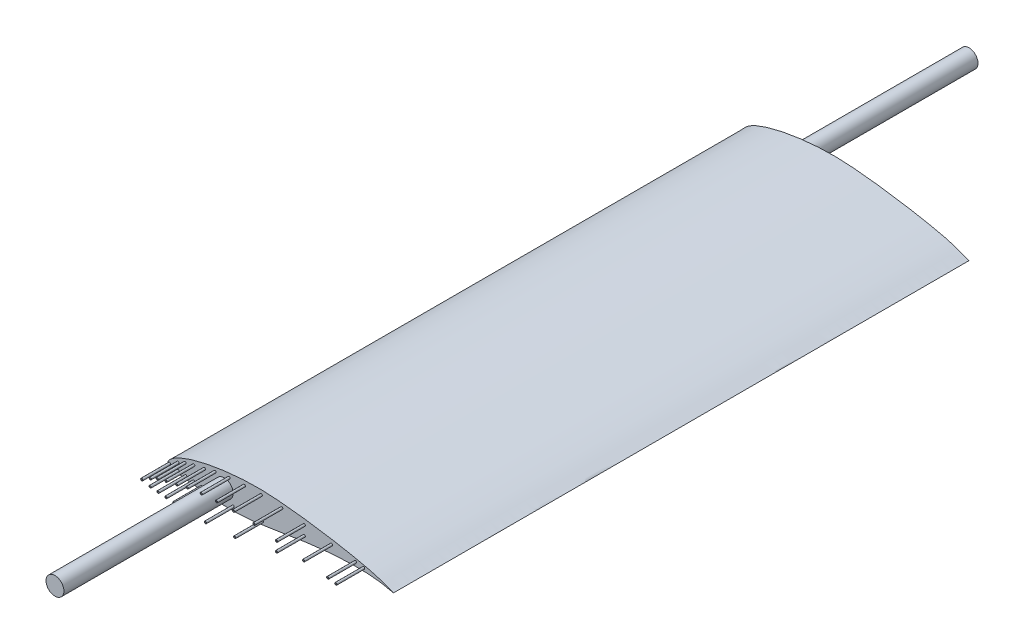
SolidWorks part; units mm, degrees
ref_plane "Front Plane" through (0, 0, 0) normal (0, 0, 1) x (1, 0, 0)
ref_plane "Top Plane" through (0, 0, 0) normal (0, 1, 0) x (1, 0, 0)
ref_plane "Right Plane" through (0, 0, 0) normal (1, 0, 0) x (0, 0, -1)
curve "Curve3"
  spline degree 3 poles (99.2573, 0.1883, 0) (100.1824, -0.0489, 0) (99.2961, 0.1993, 0) (98.6191, 0.462, 0) (97.0519, 1.0473, 0) (95.2309, 1.7549, 0) (92.9378, 2.5568, 0) (90.2536, 3.3336, 0) (87.1477, 4.0816, 0) (83.6535, 4.8449, 0) (79.8051, 5.6126, 0) (75.6551, 6.3782, 0) (71.2568, 7.1284, 0) (66.6666, 7.8484, 0) (61.9423, 8.5212, 0) (57.142, 9.1269, 0) (52.3233, 9.6447, 0) (47.5422, 10.0467, 0) (42.8474, 10.3157, 0) (38.2509, 10.3642, 0) (33.7665, 10.1859, 0) (29.4045, 9.86, 0) (25.2057, 9.3963, 0) (21.2146, 8.8145, 0) (17.4732, 8.1296, 0) (14.0211, 7.3557, 0) (10.8932, 6.51, 0) (8.1211, 5.6039, 0) (5.7296, 4.6586, 0) (3.7392, 3.6865, 0) (2.1629, 2.7162, 0) (1.0057, 1.7671, 0) (0.3099, 0.9241, 0) (0.0336, 0.3269, 0) (0.0006, 0.059, 0) (-0.0005, -0.0441, 0) (0.0087, -0.1472, 0) (0.0976, -0.2807, 0) (0.2176, -0.4056, 0) (0.6069, -0.7185, 0) (1.5156, -1.1239, 0) (3.0705, -1.583, 0) (5.1523, -2.0072, 0) (7.7279, -2.3917, 0) (10.7759, -2.7499, 0) (14.2511, -3.0772, 0) (18.0407, -3.4773, 0) (22.0414, -3.9067, 0) (26.2166, -4.1171, 0) (30.5565, -4.0983, 0) (35.1014, -3.8476, 0) (39.8555, -3.2929, 0) (44.8531, -2.5697, 0) (50.0777, -1.6972, 0) (55.4969, -0.8089, 0) (61.0345, 0.0244, 0) (66.5901, 0.7423, 0) (72.0549, 1.3013, 0) (77.3167, 1.6728, 0) (82.2608, 1.8417, 0) (86.7784, 1.812, 0) (90.7289, 1.5797, 0) (94.0476, 1.182, 0) (96.5243, 0.7715, 0) (98.476, 0.3569, 0) (99.2573, 0.1883, 0) (100.1824, -0.0489, 0) (99.2961, 0.1993, 0) knots -0.015875 -0.006971 -0.001726 0 0.001709 0.006655 0.014348 0.024259 0.036042 0.049641 0.065255 0.082793 0.102031 0.122721 0.144597 0.167375 0.190768 0.214483 0.238233 0.261741 0.284747 0.307088 0.329034 0.350455 0.371139 0.39089 0.409512 0.426831 0.442689 0.45695 0.469523 0.480322 0.48935 0.49658 0.502135 0.505254 0.506016 0.506063 0.506764 0.507486 0.508356 0.509304 0.514776 0.522722 0.53308 0.54584 0.560863 0.578018 0.596961 0.616675 0.636937 0.658148 0.680211 0.703561 0.728221 0.754164 0.781136 0.808649 0.836174 0.86317 0.889092 0.913409 0.935618 0.955187 0.97148 0.984125 0.993029 0.998274 1 1.001709 1.006655 1.014348 periodic
sketch "Sketch4" plane through (0, 0, 0) normal (0, 0, 1) x (1, 0, 0)
  spline S0 degree 3 poles (99.2573, 0.1883) (100.1824, -0.0489) (99.2961, 0.1993) (98.6191, 0.462) (97.0519, 1.0473) (95.2309, 1.7549) (92.9378, 2.5568) (90.2536, 3.3336) (87.1477, 4.0816) (83.6535, 4.8449) (79.8051, 5.6126) (75.6551, 6.3782) (71.2568, 7.1284) (66.6666, 7.8484) (61.9423, 8.5212) (57.142, 9.1269) (52.3233, 9.6447) (47.5422, 10.0467) (42.8474, 10.3157) (38.2509, 10.3642) (33.7665, 10.1859) (29.4045, 9.86) (25.2057, 9.3963) (21.2146, 8.8145) (17.4732, 8.1296) (14.0211, 7.3557) (10.8932, 6.51) (8.1211, 5.6039) (5.7296, 4.6586) (3.7392, 3.6865) (2.1629, 2.7162) (1.0057, 1.7671) (0.3099, 0.9241) (0.0336, 0.3269) (0.0006, 0.059) (-0.0005, -0.0441) (0.0087, -0.1472) (0.0976, -0.2807) (0.2176, -0.4056) (0.6069, -0.7185) (1.5156, -1.1239) (3.0705, -1.583) (5.1523, -2.0072) (7.7279, -2.3917) (10.7759, -2.7499) (14.2511, -3.0772) (18.0407, -3.4773) (22.0414, -3.9067) (26.2166, -4.1171) (30.5565, -4.0983) (35.1014, -3.8476) (39.8555, -3.2929) (44.8531, -2.5697) (50.0777, -1.6972) (55.4969, -0.8089) (61.0345, 0.0244) (66.5901, 0.7423) (72.0549, 1.3013) (77.3167, 1.6728) (82.2608, 1.8417) (86.7784, 1.812) (90.7289, 1.5797) (94.0476, 1.182) (96.5243, 0.7715) (98.476, 0.3569) (99.2573, 0.1883) (100.1824, -0.0489) (99.2961, 0.1993) knots -0.015875 -0.006971 -0.001726 0 0.001709 0.006655 0.014348 0.024259 0.036042 0.049641 0.065255 0.082793 0.102031 0.122721 0.144597 0.167375 0.190768 0.214483 0.238233 0.261741 0.284747 0.307088 0.329034 0.350455 0.371139 0.39089 0.409512 0.426831 0.442689 0.45695 0.469523 0.480322 0.48935 0.49658 0.502135 0.505254 0.506016 0.506063 0.506764 0.507486 0.508356 0.509304 0.514776 0.522722 0.53308 0.54584 0.560863 0.578018 0.596961 0.616675 0.636937 0.658148 0.680211 0.703561 0.728221 0.754164 0.781136 0.808649 0.836174 0.86317 0.889092 0.913409 0.935618 0.955187 0.97148 0.984125 0.993029 0.998274 1 1.001709 1.006655 1.014348 only from (100, 0) to (100, 0) construction
  spline S1 degree 3 poles (99.2573, 0.1883) (100.1824, -0.0489) (99.2961, 0.1993) (98.6191, 0.462) (97.0519, 1.0473) (95.2309, 1.7549) (92.9378, 2.5568) (90.2536, 3.3336) (87.1477, 4.0816) (83.6535, 4.8449) (79.8051, 5.6126) (75.6551, 6.3782) (71.2568, 7.1284) (66.6666, 7.8484) (61.9423, 8.5212) (57.142, 9.1269) (52.3233, 9.6447) (47.5422, 10.0467) (42.8474, 10.3157) (38.2509, 10.3642) (33.7665, 10.1859) (29.4045, 9.86) (25.2057, 9.3963) (21.2146, 8.8145) (17.4732, 8.1296) (14.0211, 7.3557) (10.8932, 6.51) (8.1211, 5.6039) (5.7296, 4.6586) (3.7392, 3.6865) (2.1629, 2.7162) (1.0057, 1.7671) (0.3099, 0.9241) (0.0336, 0.3269) (0.0006, 0.059) (-0.0005, -0.0441) (0.0087, -0.1472) (0.0976, -0.2807) (0.2176, -0.4056) (0.6069, -0.7185) (1.5156, -1.1239) (3.0705, -1.583) (5.1523, -2.0072) (7.7279, -2.3917) (10.7759, -2.7499) (14.2511, -3.0772) (18.0407, -3.4773) (22.0414, -3.9067) (26.2166, -4.1171) (30.5565, -4.0983) (35.1014, -3.8476) (39.8555, -3.2929) (44.8531, -2.5697) (50.0777, -1.6972) (55.4969, -0.8089) (61.0345, 0.0244) (66.5901, 0.7423) (72.0549, 1.3013) (77.3167, 1.6728) (82.2608, 1.8417) (86.7784, 1.812) (90.7289, 1.5797) (94.0476, 1.182) (96.5243, 0.7715) (98.476, 0.3569) (99.2573, 0.1883) (100.1824, -0.0489) (99.2961, 0.1993) knots -0.015875 -0.006971 -0.001726 0 0.001709 0.006655 0.014348 0.024259 0.036042 0.049641 0.065255 0.082793 0.102031 0.122721 0.144597 0.167375 0.190768 0.214483 0.238233 0.261741 0.284747 0.307088 0.329034 0.350455 0.371139 0.39089 0.409512 0.426831 0.442689 0.45695 0.469523 0.480322 0.48935 0.49658 0.502135 0.505254 0.506016 0.506063 0.506764 0.507486 0.508356 0.509304 0.514776 0.522722 0.53308 0.54584 0.560863 0.578018 0.596961 0.616675 0.636937 0.658148 0.680211 0.703561 0.728221 0.754164 0.781136 0.808649 0.836174 0.86317 0.889092 0.913409 0.935618 0.955187 0.97148 0.984125 0.993029 0.998274 1 1.001709 1.006655 1.014348 only from (100, 0) to (100, 0)
extrude "Boss-Extrude12" add sketch "Sketch4" along normal mid plane 255
sketch "Sketch5" plane through (0, 0, 127.5) normal (0, 0, 1) x (1, 0, 0)
  line L0 (100, 0) -> (100, 7.5325) construction
  circle A1 centre (25, 2.7) radius 3.9688
  spline S0 degree 3 poles (99.2573, 0.1883) (100.1824, -0.0489) (99.2961, 0.1993) (98.6191, 0.462) (97.0519, 1.0473) (95.2309, 1.7549) (92.9378, 2.5568) (90.2536, 3.3336) (87.1477, 4.0816) (83.6535, 4.8449) (79.8051, 5.6126) (75.6551, 6.3782) (71.2568, 7.1284) (66.6666, 7.8484) (61.9423, 8.5212) (57.142, 9.1269) (52.3233, 9.6447) (47.5422, 10.0467) (42.8474, 10.3157) (38.2509, 10.3642) (33.7665, 10.1859) (29.4045, 9.86) (25.2057, 9.3963) (21.2146, 8.8145) (17.4732, 8.1296) (14.0211, 7.3557) (10.8932, 6.51) (8.1211, 5.6039) (5.7296, 4.6586) (3.7392, 3.6865) (2.1629, 2.7162) (1.0057, 1.7671) (0.3099, 0.9241) (0.0336, 0.3269) (0.0006, 0.059) (-0.0005, -0.0441) (0.0087, -0.1472) (0.0976, -0.2807) (0.2176, -0.4056) (0.6069, -0.7185) (1.5156, -1.1239) (3.0705, -1.583) (5.1523, -2.0072) (7.7279, -2.3917) (10.7759, -2.7499) (14.2511, -3.0772) (18.0407, -3.4773) (22.0414, -3.9067) (26.2166, -4.1171) (30.5565, -4.0983) (35.1014, -3.8476) (39.8555, -3.2929) (44.8531, -2.5697) (50.0777, -1.6972) (55.4969, -0.8089) (61.0345, 0.0244) (66.5901, 0.7423) (72.0549, 1.3013) (77.3167, 1.6728) (82.2608, 1.8417) (86.7784, 1.812) (90.7289, 1.5797) (94.0476, 1.182) (96.5243, 0.7715) (98.476, 0.3569) (99.2573, 0.1883) (100.1824, -0.0489) (99.2961, 0.1993) knots -0.015875 -0.006971 -0.001726 0 0.001709 0.006655 0.014348 0.024259 0.036042 0.049641 0.065255 0.082793 0.102031 0.122721 0.144597 0.167375 0.190768 0.214483 0.238233 0.261741 0.284747 0.307088 0.329034 0.350455 0.371139 0.39089 0.409512 0.426831 0.442689 0.45695 0.469523 0.480322 0.48935 0.49658 0.502135 0.505254 0.506016 0.506063 0.506764 0.507486 0.508356 0.509304 0.514776 0.522722 0.53308 0.54584 0.560863 0.578018 0.596961 0.616675 0.636937 0.658148 0.680211 0.703561 0.728221 0.754164 0.781136 0.808649 0.836174 0.86317 0.889092 0.913409 0.935618 0.955187 0.97148 0.984125 0.993029 0.998274 1 1.001709 1.006655 1.014348 only from (100, 0) to (100, 0) construction
  dimension "D4" = 7.9375
  dimension "D1" = 100
  dimension "D2" = 25
  dimension "D3" = 2.7
extrude "Boss-Extrude13" add sketch "Sketch5" along normal blind 75
mirror "Mirror1" about plane through (0, 0, 0) normal (0, 0, 1) of "Boss-Extrude13"
sketch "Sketch6" plane through (0, 0, 127.5) normal (0, 0, 1) x (1, 0, 0)
  line L0 (51.5475, 9.6988) -> (56.9104, 9.1388) construction
  line L1 (41.449, 10.3172) -> (44.1311, 10.2279) construction
  circle A0 centre (0.75, 0) radius 0.495
  circle A1 centre (0.75, 0) radius 0.325
  circle A2 centre (86.76, 3) radius 0.495
  circle A3 centre (86.76, 3) radius 0.325
  circle A4 centre (83.16, 3.5) radius 0.495
  circle A5 centre (83.16, 3.5) radius 0.325
  circle A6 centre (72.5, 4.8) radius 0.495
  circle A7 centre (72.5, 4.8) radius 0.325
  circle A8 centre (60.4429, 6.3) radius 0.495
  circle A9 centre (60.4429, 6.3) radius 0.325
  circle A10 centre (60.4429, 2.15) radius 0.495
  circle A11 centre (60.4429, 2.15) radius 0.325
  circle A12 centre (50.4652, 7.8009) radius 0.495
  circle A13 centre (50.4652, 7.8009) radius 0.325
  circle A14 centre (41.4199, 8.317) radius 0.495
  circle A15 centre (41.4199, 8.317) radius 0.325
  circle A16 centre (41.4199, 8.317) radius 0.495
  circle A17 centre (41.4199, 8.317) radius 0.325
  circle A18 centre (33.8799, 8.117) radius 0.495
  circle A19 centre (33.8799, 8.117) radius 0.325
  circle A20 centre (27.1399, 7.767) radius 0.495
  circle A21 centre (27.1399, 7.767) radius 0.325
  circle A22 centre (20.9099, 6.967) radius 0.495
  circle A23 centre (20.9099, 6.967) radius 0.325
  circle A26 centre (16.221, 5.767) radius 0.495
  circle A27 centre (16.221, 5.767) radius 0.325
  circle A28 centre (11.4855, 4.767) radius 0.495
  circle A29 centre (11.4855, 4.767) radius 0.325
  circle A30 centre (7.6125, 3.767) radius 0.495
  circle A31 centre (7.6125, 3.767) radius 0.325
  circle A36 centre (4.5056, 2.267) radius 0.495
  circle A37 centre (4.5056, 2.267) radius 0.325
  circle A38 centre (4.5056, -0.85) radius 0.495
  circle A39 centre (4.5056, -0.85) radius 0.325
  circle A40 centre (7.9928, -1.15) radius 0.495
  circle A41 centre (7.9928, -1.15) radius 0.325
  circle A42 centre (11.4799, -1.45) radius 0.495
  circle A43 centre (11.4799, -1.45) radius 0.325
  circle A44 centre (14.9569, -1.85) radius 0.495
  circle A45 centre (14.9569, -1.85) radius 0.325
  circle A46 centre (28.948, -2.35) radius 0.495
  circle A47 centre (28.948, -2.35) radius 0.325
  circle A48 centre (41.9234, -1.55) radius 0.495
  circle A49 centre (41.9234, -1.55) radius 0.325
  spline S2 degree 3 poles (99.2573, 0.1883) (100.1824, -0.0489) (99.2961, 0.1993) (98.6191, 0.462) (97.0519, 1.0473) (95.2309, 1.7549) (92.9378, 2.5568) (90.2536, 3.3336) (87.1477, 4.0816) (83.6535, 4.8449) (79.8051, 5.6126) (75.6551, 6.3782) (71.2568, 7.1284) (66.6666, 7.8484) (61.9423, 8.5212) (57.142, 9.1269) (52.3233, 9.6447) (47.5422, 10.0467) (42.8474, 10.3157) (38.2509, 10.3642) (33.7665, 10.1859) (29.4045, 9.86) (25.2057, 9.3963) (21.2146, 8.8145) (17.4732, 8.1296) (14.0211, 7.3557) (10.8932, 6.51) (8.1211, 5.6039) (5.7296, 4.6586) (3.7392, 3.6865) (2.1629, 2.7162) (1.0057, 1.7671) (0.3099, 0.9241) (0.0336, 0.3269) (0.0006, 0.059) (-0.0005, -0.0441) (0.0087, -0.1472) (0.0976, -0.2807) (0.2176, -0.4056) (0.6069, -0.7185) (1.5156, -1.1239) (3.0705, -1.583) (5.1523, -2.0072) (7.7279, -2.3917) (10.7759, -2.7499) (14.2511, -3.0772) (18.0407, -3.4773) (22.0414, -3.9067) (26.2166, -4.1171) (30.5565, -4.0983) (35.1014, -3.8476) (39.8555, -3.2929) (44.8531, -2.5697) (50.0777, -1.6972) (55.4969, -0.8089) (61.0345, 0.0244) (66.5901, 0.7423) (72.0549, 1.3013) (77.3167, 1.6728) (82.2608, 1.8417) (86.7784, 1.812) (90.7289, 1.5797) (94.0476, 1.182) (96.5243, 0.7715) (98.476, 0.3569) (99.2573, 0.1883) (100.1824, -0.0489) (99.2961, 0.1993) knots -0.015875 -0.006971 -0.001726 0 0.001709 0.006655 0.014348 0.024259 0.036042 0.049641 0.065255 0.082793 0.102031 0.122721 0.144597 0.167375 0.190768 0.214483 0.238233 0.261741 0.284747 0.307088 0.329034 0.350455 0.371139 0.39089 0.409512 0.426831 0.442689 0.45695 0.469523 0.480322 0.48935 0.49658 0.502135 0.505254 0.506016 0.506063 0.506764 0.507486 0.508356 0.509304 0.514776 0.522722 0.53308 0.54584 0.560863 0.578018 0.596961 0.616675 0.636937 0.658148 0.680211 0.703561 0.728221 0.754164 0.781136 0.808649 0.836174 0.86317 0.889092 0.913409 0.935618 0.955187 0.97148 0.984125 0.993029 0.998274 1 1.001709 1.006655 1.014348 only from (100, 0) to (100, 0) construction
  spline S3 degree 3 poles (99.2573, 0.1883) (100.1824, -0.0489) (99.2961, 0.1993) (98.6191, 0.462) (97.0519, 1.0473) (95.2309, 1.7549) (92.9378, 2.5568) (90.2536, 3.3336) (87.1477, 4.0816) (83.6535, 4.8449) (79.8051, 5.6126) (75.6551, 6.3782) (71.2568, 7.1284) (66.6666, 7.8484) (61.9423, 8.5212) (57.142, 9.1269) (52.3233, 9.6447) (47.5422, 10.0467) (42.8474, 10.3157) (38.2509, 10.3642) (33.7665, 10.1859) (29.4045, 9.86) (25.2057, 9.3963) (21.2146, 8.8145) (17.4732, 8.1296) (14.0211, 7.3557) (10.8932, 6.51) (8.1211, 5.6039) (5.7296, 4.6586) (3.7392, 3.6865) (2.1629, 2.7162) (1.0057, 1.7671) (0.3099, 0.9241) (0.0336, 0.3269) (0.0006, 0.059) (-0.0005, -0.0441) (0.0087, -0.1472) (0.0976, -0.2807) (0.2176, -0.4056) (0.6069, -0.7185) (1.5156, -1.1239) (3.0705, -1.583) (5.1523, -2.0072) (7.7279, -2.3917) (10.7759, -2.7499) (14.2511, -3.0772) (18.0407, -3.4773) (22.0414, -3.9067) (26.2166, -4.1171) (30.5565, -4.0983) (35.1014, -3.8476) (39.8555, -3.2929) (44.8531, -2.5697) (50.0777, -1.6972) (55.4969, -0.8089) (61.0345, 0.0244) (66.5901, 0.7423) (72.0549, 1.3013) (77.3167, 1.6728) (82.2608, 1.8417) (86.7784, 1.812) (90.7289, 1.5797) (94.0476, 1.182) (96.5243, 0.7715) (98.476, 0.3569) (99.2573, 0.1883) (100.1824, -0.0489) (99.2961, 0.1993) knots -0.015875 -0.006971 -0.001726 0 0.001709 0.006655 0.014348 0.024259 0.036042 0.049641 0.065255 0.082793 0.102031 0.122721 0.144597 0.167375 0.190768 0.214483 0.238233 0.261741 0.284747 0.307088 0.329034 0.350455 0.371139 0.39089 0.409512 0.426831 0.442689 0.45695 0.469523 0.480322 0.48935 0.49658 0.502135 0.505254 0.506016 0.506063 0.506764 0.507486 0.508356 0.509304 0.514776 0.522722 0.53308 0.54584 0.560863 0.578018 0.596961 0.616675 0.636937 0.658148 0.680211 0.703561 0.728221 0.754164 0.781136 0.808649 0.836174 0.86317 0.889092 0.913409 0.935618 0.955187 0.97148 0.984125 0.993029 0.998274 1 1.001709 1.006655 1.014348 only from (100, 0) to (100, 0)
  dimension "D1" = 0.99
  dimension "D2" = 0.75
  dimension "D3" = 0.65
  dimension "D4" = 0.99
  dimension "D5" = 0.65
  dimension "D7" = 3
  dimension "D8" = 0.99
  dimension "D11" = 0.65
  dimension "D14" = 0.99
  dimension "D15" = 0.65
  dimension "D16" = 0.99
  dimension "D19" = 0.65
  dimension "D20" = 0.99
  dimension "D21" = 0.65
  dimension "D24" = 0.99
  dimension "D25" = 0.65
  dimension "D28" = 0.99
  dimension "D32" = 0.65
  dimension "D35" = 0.99
  dimension "D36" = 0.65
  dimension "D39" = 0.99
  dimension "D40" = 0.65
  dimension "D42" = 0.99
  dimension "D43" = 0.65
  dimension "D46" = 0.99
  dimension "D47" = 0.65
  dimension "D50" = 0.99
  dimension "D51" = 0.65
  dimension "D54" = 0.99
  dimension "D55" = 0.65
  dimension "D58" = 0.99
  dimension "D59" = 0.65
  dimension "D60" = 0.99
  dimension "D61" = 0.65
  dimension "D62" = 0.99
  dimension "D63" = 0.65
  dimension "D64" = 0.99
  dimension "D65" = 0.65
  dimension "D66" = 0.99
  dimension "D67" = 0.65
  dimension "D68" = 0.65
  dimension "D69" = 0.99
  dimension "D70" = 0.99
  dimension "D71" = 0.65
  dimension "D6" = 13.24
  dimension "D9" = 3.6
  dimension "D10" = 0.5
  dimension "D12" = 10.66
  dimension "D13" = 1.3
  dimension "D17" = 12.15
  dimension "D18" = 1.5
  dimension "D22" = 4.15
  dimension "D23" = 4.84
  dimension "D26" = 10.09
  dimension "D27" = 1.5009
  dimension "D29" = 9.06
  dimension "D30" = 2
  dimension "D31" = 0.5161
  dimension "D33" = 7.54
  dimension "D34" = 0.2
  dimension "D37" = 6.74
  dimension "D38" = 0.35
  dimension "D41" = 6.23
  dimension "D44" = 0.8
  dimension "D45" = 1.2
  dimension "D48" = 4.84
  dimension "D49" = 1
  dimension "D52" = 4
  dimension "D53" = 1
  dimension "D56" = 3.45
  dimension "D57" = 1.5
  dimension "D72" = 0.85
  dimension "D73" = 3.5
  dimension "D74" = 0.3
  dimension "D75" = 3.5
  dimension "D76" = 0.3
  dimension "D77" = 3.5
  dimension "D78" = 0.4
  dimension "D79" = 14
  dimension "D80" = 0.5
  dimension "D81" = 13
  dimension "D82" = 0.8
extrude "Boss-Extrude14" add sketch "Sketch6" along normal blind 12.3 contours A14 A15 | A12 A13 | A8 A9 | A10 A11 | A6 A7 | A4 A5 | A2 A3 | A18 | A20 | A22 | A23 | A21 | A19 | A26 | A28 | A29 | A27 | A31 | A30 | A40 | A41 | A42 | A43 | A44 | A45 | A46 | A47 | A48 | A49 | A0 | A1 | A36 | A37 | A38 | A39 region at (86.279, 3, 127.5) region at (82.679, 3.5, 127.5) region at (72.019, 4.8, 127.5) region at (59.9619, 6.3, 127.5) region at (59.9619, 2.15, 127.5) region at (49.9842, 7.8009, 127.5) region at (40.9389, 8.317, 127.5)
